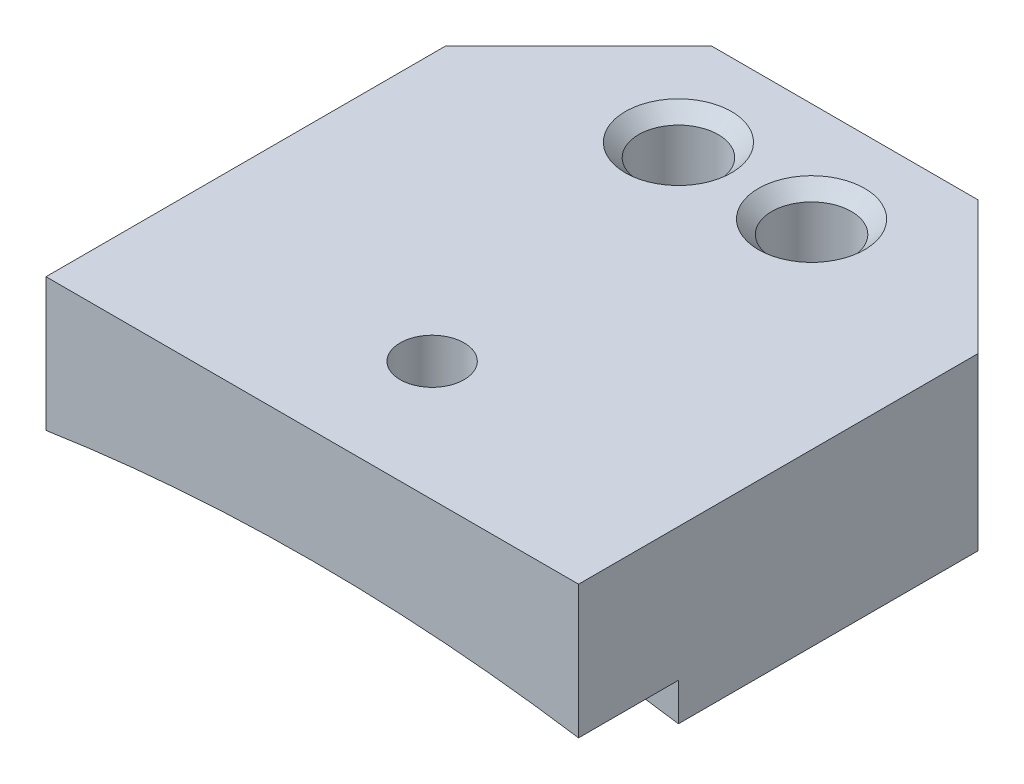
SolidWorks part; units mm, degrees
ref_plane "Front Plane" through (0, 0, 0) normal (0, 0, 1) x (1, 0, 0)
ref_plane "Top Plane" through (0, 0, 0) normal (0, 1, 0) x (1, 0, 0)
ref_plane "Right Plane" through (0, 0, 0) normal (1, 0, 0) x (0, 0, -1)
sketch "Sketch1" plane through (0, 0, 0) normal (0, 1, 0) x (1, 0, 0)
  line L0 (-28.5118, 6.4953) -> (-22.1618, 12.8453)
  line L1 (-22.1618, 12.8453) -> (-9.4618, 12.8453)
  line L2 (-28.5118, 6.4953) -> (-28.5118, -12.5547)
  line L3 (-28.5118, -12.5547) -> (-3.1118, -12.5547)
  line L4 (-3.1118, 6.4953) -> (-3.1118, -12.5547)
  line L5 (-9.4618, 12.8453) -> (-3.1118, 6.4953)
  line L6 (-15.8118, -12.5547) -> (-15.8118, 12.8453) construction
  line L8 (-3.1118, 6.4953) -> (-3.1118, 12.8453) construction
  line L9 (-3.1118, 12.8453) -> (-9.4618, 12.8453) construction
  dimension "D1" = 12.7
  dimension "D2" = 25.4
  dimension "D3" = 25.4
extrude "Boss-Extrude1" add sketch "Sketch1" along normal blind 6.35
sketch "Sketch2" plane through (0, 0, 12.5547) normal (0, 0, 1) x (1, 0, 0)
  circle A0 centre (-15.8118, -82.8523) radius 83.82
  dimension "D1" = 167.64
extrude "Cut-Extrude1" cut sketch "Sketch2" against normal through all both and the other way through all
sketch "Sketch5" plane through (0, 0, -12.8453) normal (0, 0, -1) x (-1, 0, 0)
  line L0 (3.1118, 6.35) -> (3.1118, 0) construction
  line L1 (3.1118, 6.35) -> (3.1118, 0)
  line L4 (28.5118, 6.35) -> (28.5118, 0) construction
  line L5 (28.5118, 6.35) -> (28.5118, 0)
  line L6 (28.5118, -1.7992) -> (28.5118, 0)
  line L7 (3.1118, -1.7992) -> (3.1118, 0)
  line L8 (3.1118, 6.35) -> (28.5118, 6.35)
  arc A0 (3.1118, -1.7992) -> (28.5118, -1.7992) centre (15.8118, -82.8523) cw
  arc A1 (28.5118, 0) -> (3.1118, 0) centre (15.8118, -82.8523) ccw construction
  arc A2 (28.5118, 0) -> (3.1118, 0) centre (15.8118, -82.8523) ccw construction
  dimension "D1" = 82.042
extrude "Boss-Extrude2" add sketch "Sketch5" against normal blind 20.6375
chamfer "Chamfer1" distance 6.35 angle 45 2 edges at (-28.5118, 2.2754, -12.8453) (-3.1118, 2.2754, -12.8453)
hole_wizard "#10-24 Tapped Hole1" positions "Sketch3" profile "Sketch4" tap size "#10-24" standard "ANSI Inch" end condition through all
sketch "Sketch3" plane through (0, 6.35, 0) normal (0, 1, 0) x (1, 0, 0)
  line L0 (-15.8118, 12.8453) -> (-15.8118, 3.4006) construction
  line L1 (-9.4618, 12.8453) -> (-22.1618, 12.8453) construction
  point P0 (-18.9868, 8.0828)
  point P12 (-12.6368, 8.0828)
  dimension "D1" = 4.7625
  dimension "D2" = 3.175
sketch "Sketch4" plane through (-18.9868, 6.35, -8.0828) normal (1, 0, 0) x (0, 0, 1)
  line L0 (0, 0) -> (0, 8.1492)
  line L1 (0, 8.1492) -> (1.8986, 8.1492)
  line L2 (1.8986, 8.1492) -> (1.8986, 0.635)
  line L3 (1.8986, 0.635) -> (2.5337, 0)
  line L5 (2.5337, 0) -> (0, 0)
  line L6 (-1.8986, 0.635) -> (-2.5337, 0) construction
  line L11 (0, -6.35) -> (0, 107.95) construction
  dimension "Thru Tap Drill Dia." = 3.7973
  dimension "Thru Tap Drill Depth" = 8.1492
  dimension "Near C'Sink Dia." = 5.0673
  dimension "Near C'Sink Angle" = 90
cosmetic thread "Hole Thread3" parameters "D2"=4.826
cosmetic thread "Hole Thread4" parameters "D2"=4.826
sketch "Sketch6" plane through (0, 6.35, 0) normal (0, 1, 0) x (1, 0, 0)
  circle A0 centre (-15.8102, -6.8397) radius 1.524 construction
  circle A1 centre (-15.8102, -6.8397) radius 1.524
extrude "Cut-Extrude2" cut sketch "Sketch6" against normal through all
